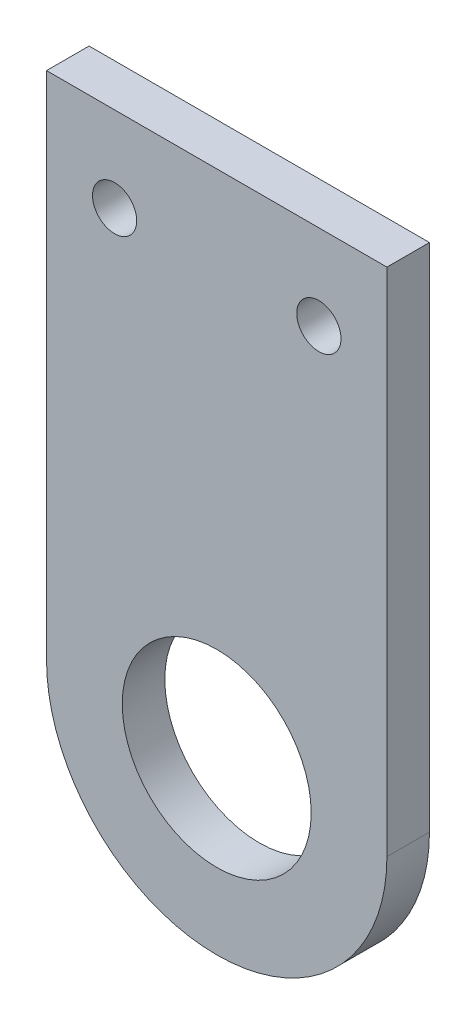
SolidWorks part; units mm, degrees
material "6061 合金"
ref_plane "前视基准面" through (0, 0, 0) normal (0, 0, 1) x (1, 0, 0)
ref_plane "上视基准面" through (0, 0, 0) normal (0, 1, 0) x (1, 0, 0)
ref_plane "右视基准面" through (0, 0, 0) normal (1, 0, 0) x (0, 0, -1)
other "Configuration Table"
sketch "草图1" plane through (0, 0, 0) normal (0, 0, 1) x (1, 0, 0)
  circle A0 centre (0, 0) radius 20
  circle A1 centre (0, 0) radius 11
  dimension "D1" = 40
  dimension "D2" = 22
extrude "凸台-拉伸1" add sketch "草图1" along normal blind 60 contours A1 | A0 region at (0, 0, 0)
ref_plane "基准面1" through (0, 0, 30) normal (0, 0, 1) x (1, 0, 0)
sketch "草图2" plane through (0, 0, 30) normal (0, 0, 1) x (1, 0, 0)
  line L0 (0, 0) -> (-70, -70) construction
  line L1 (-70, -70) -> (-70, -320) construction
  line L2 (0, -57.3148) -> (0, 49.9409) construction
  line L3 (-56.8582, 0) -> (46.4003, 0) construction
  line L4 (-14.1421, 14.1421) -> (-90, -61.7157)
  line L5 (14.1421, -14.1421) -> (-50, -78.2843)
  line L6 (-90, -61.7157) -> (-90, -320)
  line L7 (-50, -78.2843) -> (-50, -320)
  line L8 (-90, -320) -> (-50, -320)
  circle A2 centre (0, 0) radius 20 construction
  arc A3 (-14.1421, 14.1421) -> (14.1421, -14.1421) centre (0, 0) ccw
  dimension "D1" = 45
  dimension "D2" = 250
  dimension "D3" = 70
  dimension "D4" = 40
  dimension "D5" = 40
extrude "凸台-拉伸2" add sketch "草图2" along normal mid plane 60 contours L7 L8 L6 L4 A3 L5
sketch "草图4" plane through (0, 0, 60) normal (0, 0, 1) x (1, 0, 0)
  line L0 (-90, -61.7157) -> (-90, -320) construction
  line L1 (-90, -290) -> (-50, -290)
  line L2 (-90, -290) -> (-90, -350)
  line L4 (-50, -290) -> (-50, -350)
  line L5 (-50, -78.2843) -> (-50, -320) construction
  line L6 (-90, -320) -> (-50, -320) construction
  arc A0 (-90, -350) -> (-50, -350) centre (-70, -350) ccw
  circle A1 centre (-70, -350) radius 11
  dimension "D3" = 22
  dimension "D1" = 30
  dimension "D2" = 30
extrude "凸台-拉伸3" add sketch "草图4" along normal blind 5
mirror "镜向1" about plane through (0, 0, 30) normal (0, 0, 1) of "凸台-拉伸3"
sketch "草图5" plane through (0, 0, 0) normal (0, 1, 0) x (1, 0, 0)
  line L0 (0, 0) -> (0, -78.0582) construction
ref_plane "基准面2" through (-70, 0, 0) normal (-1, 0, 0) x (0, 0, 1)
sketch "草图7" plane through (-70, 0, 0) normal (-1, 0, 0) x (0, 0, 1)
  line L0 (-34.1239, -350) -> (109.535, -350) construction
sketch "草图8" plane through (0, 0, 60) normal (0, 0, 1) x (1, 0, 0)
  line L0 (0, 0) -> (-70, -70) construction
  circle A0 centre (-35.3553, -35.3553) radius 11
  dimension "D1" = 22
  dimension "D2" = 50
extrude "切除-拉伸1" cut sketch "草图8" against normal blind 100
fillet "圆角4" radius 20 2 edges at (-90, -61.7157, 30) (-50, -78.2843, 30)
fillet "圆角1" [suppressed] radius 50
fillet "圆角2" [suppressed] radius 3
sketch "草图9" plane through (0, 0, 65) normal (0, 0, 1) x (1, 0, 0)
  circle A0 centre (-70, -350) radius 13
  dimension "D1" = 26
extrude "切除-拉伸2" [suppressed] cut sketch "草图9" against normal blind 0.75
sketch "草图10" plane through (0, 0, -5) normal (0, 0, -1) x (-1, 0, 0)
  circle A0 centre (70, -350) radius 13
  dimension "D1" = 26
extrude "切除-拉伸3" [suppressed] cut sketch "草图10" against normal blind 0.75 contours A0
sketch "草图11" plane through (-90, 0, 0) normal (-1, 0, 0) x (0, 0, 1)
  circle A0 centre (48.5, -118.9949) radius 2.75
  circle A1 centre (48.5, -183.9949) radius 2.75
  circle A2 centre (48.5, -248.9949) radius 2.75
  circle A3 centre (11.5, -248.9949) radius 2.75
  circle A4 centre (11.5, -183.9949) radius 2.75
  circle A5 centre (11.5, -118.9949) radius 2.75
  dimension "D1" = 5.5
extrude "切除-拉伸4" [suppressed] cut sketch "草图11" against normal through all contours A1 | A2 | A0 | A3 | A4 | A5
sketch "草图12" [suppressed] plane through (-90, 0, 0) normal (-1, 0, 0) x (0, 0, 1)
  line L0 (30, -62.0134) -> (30, -339.6946) construction
  line L1 (10, -128.9949) -> (50, -128.9949)
  line L2 (10, -128.9949) -> (10, -173.9949)
  line L3 (10, -173.9949) -> (50, -173.9949)
  line L4 (50, -128.9949) -> (50, -173.9949)
  line L5 (10, -193.9949) -> (50, -193.9949)
  line L6 (10, -193.9949) -> (10, -238.9949)
  line L7 (10, -238.9949) -> (50, -238.9949)
  line L8 (50, -193.9949) -> (50, -238.9949)
  line L9 (10, -258.9949) -> (50, -258.9949)
  line L10 (10, -258.9949) -> (10, -290)
  line L11 (10, -290) -> (50, -290)
  line L12 (50, -258.9949) -> (50, -290)
  line L13 (19.5, -173.9949) -> (40.5, -173.9949)
  line L14 (19.5, -173.9949) -> (19.5, -193.9949)
  line L15 (19.5, -193.9949) -> (40.5, -193.9949)
  line L16 (40.5, -173.9949) -> (40.5, -193.9949)
  line L17 (19.5, -238.9949) -> (40.5, -238.9949)
  line L18 (19.5, -238.9949) -> (19.5, -258.9949)
  line L19 (19.5, -258.9949) -> (40.5, -258.9949)
  line L20 (40.5, -238.9949) -> (40.5, -258.9949)
  line L21 (60, -82.4264) -> (60, -290) construction
  line L22 (0, -290) -> (0, -82.4264) construction
  line L23 (57, -320) -> (3, -320) construction
  circle A0 centre (48.5, -118.9949) radius 2.75 construction
  circle A1 centre (48.5, -183.9949) radius 2.75 construction
  circle A2 centre (48.5, -248.9949) radius 2.75 construction
  dimension "D1" = 10
  dimension "D2" = 10
  dimension "D3" = 10
  dimension "D4" = 8
  dimension "D5" = 10
  dimension "D6" = 10
  dimension "D7" = 10
  dimension "D8" = 30
extrude "减重" [suppressed] cut sketch "草图12" against normal through all contours L0 L1 L2 L3 | L15 L0 L17 L7 L8 L5 | L0 L5 L6 L7 | L19 L0 L11 L12 L9 | L0 L9 L10 L11 | L1 L0 L13 L3 L4
fillet "圆角3" [suppressed] radius 3
sketch "草图13" plane through (0, 0, 60) normal (0, 0, 1) x (1, 0, 0)
  circle A0 centre (0, 0) radius 13
  circle A1 centre (-35.3553, -35.3553) radius 13
  dimension "D1" = 26
  dimension "D2" = 26
extrude "切除-拉伸6" [suppressed] cut sketch "草图13" against normal blind 1.75
sketch "草图14" plane through (0, 0, 0) normal (0, 0, -1) x (-1, 0, 0)
  circle A0 centre (0, 0) radius 13
  circle A1 centre (35.3553, -35.3553) radius 13
  dimension "D1" = 26
  dimension "D2" = 26
extrude "切除-拉伸7" [suppressed] cut sketch "草图14" against normal blind 1.75
sketch "草图15" [suppressed] plane through (0, 0, 0) normal (0, 0, -1) x (-1, 0, 0)
  line L0 (0, 0) -> (70, -350) construction
  line L1 (56.2719, -67.2005) -> (60.1942, -86.8121) construction
  line L2 (70, -350) -> (204.3541, -323.1292) construction
  circle A0 centre (56.2719, -67.2005) radius 2.75
  circle A1 centre (75.2172, -73.6095) radius 2.75
  circle A2 centre (60.1942, -86.8121) radius 2.75
  dimension "D1" = 5.5
  dimension "D2" = 20
  dimension "D3" = 20
  dimension "D4" = 20
  dimension "D5" = 42
  dimension "D6" = 270
extrude "切除-拉伸8" [suppressed] cut sketch "草图15" against normal through all contours A2 | A0 | A1
ref_plane "小腿主干连杆面" through (0, 0, 0) normal (0.9806, -0.1961, 0) x (0, 0, -1)
ref_plane "小腿主干对称面" through (0, 0, 30) normal (0, 0, -1) x (-1, 0, 0)
sketch "草图16" plane through (0, 0, 60) normal (0, 0, 1) x (1, 0, 0)
  line L0 (0, 0) -> (-70, -350)
  line L1 (-35.3553, -35.3553) -> (0, 0)
sketch "草图17" plane through (0, 0, 60) normal (0, 0, 1) x (1, 0, 0)
  line L0 (0, 0) -> (-70, -350) construction
  line L1 (118.6974, 32.5948) -> (32.9122, -396.3312) construction
  line L2 (92.7764, -97.0102) -> (20.2919, -82.5133)
  line L3 (73.1648, -195.0683) -> (0.6803, -180.5713)
  circle A0 centre (20.2919, -82.5133) radius 46
  circle A1 centre (0.6803, -180.5713) radius 46
  dimension "D3" = 92
  dimension "D4" = 92
  dimension "D1" = 110
  dimension "D2" = 73.92
  dimension "D5" = 180
  dimension "D6" = 280
sketch "草图18" plane through (0, 0, 60) normal (0, 0, 1) x (1, 0, 0)
  line L1 (14.1421, -14.1421) -> (-44.1421, -72.4264) construction
  line L3 (14.1421, -14.1421) -> (-44.1421, -72.4264)
  line L4 (15.4873, -12.6548) -> (52.8188, -49.9864)
  line L5 (-50, -128.5133) -> (20.2919, -128.5133)
  line L10 (-90, -290) -> (-50, -290)
  line L11 (-50, -290) -> (-50, -86.5685)
  line L12 (-44.1421, -72.4264) -> (14.1421, -14.1421)
  line L13 (-14.1421, 14.1421) -> (-84.1421, -55.8579)
  line L14 (-90, -70) -> (-90, -290)
  line L16 (-50, -128.5133) -> (-50, -86.5685)
  line L17 (-44.1421, -72.4264) -> (14.1421, -14.1421)
  circle A0 centre (20.2919, -82.5133) radius 46 construction
  arc A1 (14.1421, -14.1421) -> (-14.1421, 14.1421) centre (0, 0) ccw construction
  arc A2 (14.1421, -14.1421) -> (-14.1421, 14.1421) centre (0, 0) ccw
  arc A3 (14.1421, -14.1421) -> (15.4873, -12.6548) centre (0, 0) ccw
  arc A4 (20.2919, -128.5133) -> (52.8188, -49.9864) centre (20.2919, -82.5133) ccw
  circle A5 centre (20.2919, -82.5133) radius 35
  arc A9 (-84.1421, -55.8579) -> (-90, -70) centre (-70, -70) ccw
  arc A10 (-84.1421, -55.8579) -> (-90, -70) centre (-70, -70) ccw
  arc A11 (-44.1421, -72.4264) -> (-50, -86.5685) centre (-30, -86.5685) ccw
  arc A12 (-44.1421, -72.4264) -> (-50, -86.5685) centre (-30, -86.5685) ccw
  line M14 (-50, -290) -> (-50, -86.5685)
  line M15 (-44.1421, -72.4264) -> (14.1421, -14.1421)
  arc M16 (14.1421, -14.1421) -> (-14.1421, 14.1421) centre (0, 0) ccw
  arc M22 (-50, -86.5685) -> (-44.1421, -72.4264) centre (-30, -86.5685) cw
  dimension "D2" = 70
  dimension "D1" = 0
extrude "凸台-拉伸4" add sketch "草图18" against normal blind 5 from offset 25 contours L5 A4 L4 A5 M16 M15 M22 M14 region at (16.0508, -14.5165, 60) offset against normal yes
sketch "草图19" plane through (0, 0, 0) normal (0, 0, -1) x (-1, 0, 0)
  line L0 (50, -86.5685) -> (50, -290) construction
  line L1 (50, -134.5713) -> (50, -226.5713)
  line L2 (-0.6803, -134.5713) -> (50, -134.5713)
  line L3 (-0.6803, -226.5713) -> (50, -226.5713)
  circle A0 centre (-0.6803, -180.5713) radius 46 construction
  arc A1 (-0.6803, -134.5713) -> (-0.6803, -226.5713) centre (-0.6803, -180.5713) ccw
  circle A2 centre (-0.6803, -180.5713) radius 35
  dimension "D1" = 70
extrude "凸台-拉伸5" add sketch "草图19" against normal blind 5 from offset 25 offset against normal yes
fillet "圆角5" radius 10 2 edges at (-50, -226.5713, 27.5) (-50, -128.5133, 32.5)
sketch "草图21" plane through (0, 0, 65) normal (0, 0, 1) x (1, 0, 0)
  line L0 (-70, -350) -> (-70, -6.9331) construction
  circle A0 centre (-70, -75) radius 2.6
  circle A1 centre (-70, -250) radius 2.6
  circle A2 centre (-58, -300) radius 2.6
  circle A3 centre (-82, -300) radius 2.6
  dimension "D1" = 5.2
  dimension "D2" = 12
  dimension "D3" = 50
  dimension "D4" = 100
  dimension "D5" = 175
extrude "切除-拉伸9" cut sketch "草图21" against normal through all both and the other way through all
sketch "草图22" plane through (-90, 0, 0) normal (-1, 0, 0) x (0, 0, 1)
  line L10 (65, -370) -> (0, -370)
  line L11 (65, -370) -> (65, 61.088)
  line L12 (65, 61.088) -> (0, 61.088)
  line L13 (0, -370) -> (0, 61.088)
  dimension "D1" = 65
extrude "切除-拉伸10" cut sketch "草图22" against normal through all both contours L13 L12 L11 L10
other "移动面1" flip direction yes face at (-59, -350, -5) offset 0.1 parameters "D1"=0.1
